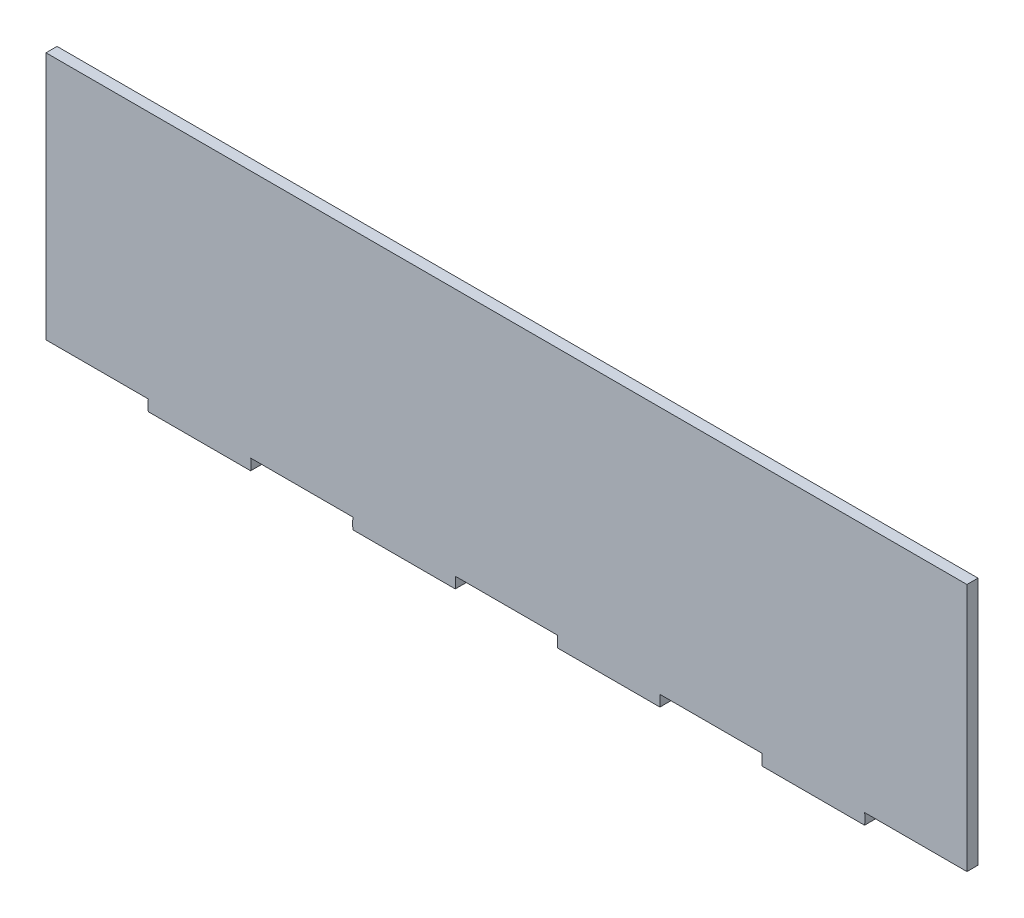
SolidWorks part; units mm, degrees
material "Pine"
ref_plane "Front Plane" through (0, 0, 0) normal (0, 0, 1) x (1, 0, 0)
ref_plane "Top Plane" through (0, 0, 0) normal (0, 1, 0) x (1, 0, 0)
ref_plane "Right Plane" through (0, 0, 0) normal (1, 0, 0) x (0, 0, -1)
sketch "Sketch1" plane through (0, 0, 0) normal (0, 0, 1) x (1, 0, 0)
  line L1 (-250, -70.5) -> (250, -70.5)
  line L2 (-250, -70.5) -> (-250, 70.5)
  line L3 (-250, 70.5) -> (250, 70.5)
  line L4 (250, -70.5) -> (250, 70.5)
  line L5 (-250, -70.5) -> (250, 70.5) construction
  line L6 (-250, 70.5) -> (250, -70.5) construction
  point P0 (0, 0)
  dimension "D1" = 500
  dimension "D2" = 141
extrude "Boss-Extrude1" add sketch "Sketch1" along normal blind 6
sketch "Sketch2" plane through (0, 0, 6) normal (0, 0, 1) x (1, 0, 0)
  line L0 (-250, -70.5) -> (250, -70.5) construction
  line L1 (194.4, -70.5) -> (138.8, -70.5)
  line L2 (194.4, -70.5) -> (194.4, -64.5)
  line L3 (194.4, -64.5) -> (138.8, -64.5)
  line L4 (138.8, -70.5) -> (138.8, -64.5)
  line L5 (250, -70.5) -> (250, 70.5) construction
  line L6 (194.4, -64.5) -> (250, -64.5)
  ellipse E0 centre (194.4, -67.5) end of major axis (194.4, -64.5) minor radius 0.2
  ellipse E1 centre (250, -67.5) end of major axis (250, -70.5) minor radius 0.2
  point P6 (138.8, -67.5)
  line M5 (-250, -70.5) -> (250, -70.5)
  dimension "D1" = 6
  dimension "D2" = 55.6
  dimension "D3" = 55.6
  dimension "D4" = 0.2
  dimension "D5" = 0.2
  dimension "D6" = 3
extrude "Cut-Extrude1" cut sketch "Sketch2" against normal blind 6 contours E1 L6 E0 M5 region at (222.2, -67.5, 6)
pattern_linear "LPattern1" count 5 spacing 111.1 along (-1, 0, 0) of "Cut-Extrude1"
sketch "Sketch3" plane through (0, 0, 6) normal (0, 0, 1) x (1, 0, 0)
  line L1 (-250, -64.5) -> (-249.4463, -64.5)
  line L2 (-250, -64.5) -> (-250, -70.5)
  line L3 (-250, -70.5) -> (-249.4463, -70.5)
  line L4 (-249.4463, -64.5) -> (-249.4463, -70.5)
  dimension "D1" = 6
  dimension "D2" = 0.5537
extrude "Cut-Extrude2" cut sketch "Sketch3" against normal blind 6
sketch "Sketch4" plane through (0, 0, 6) normal (0, 0, 1) x (1, 0, 0)
  line L1 (250, -64.5) -> (249.3874, -64.5)
  line L2 (250, -64.5) -> (250, -70.5)
  line L3 (250, -70.5) -> (249.3874, -70.5)
  line L4 (249.3874, -64.5) -> (249.3874, -70.5)
  dimension "D1" = 6
  dimension "D2" = 0.6126
extrude "Cut-Extrude3" cut sketch "Sketch4" against normal blind 6
